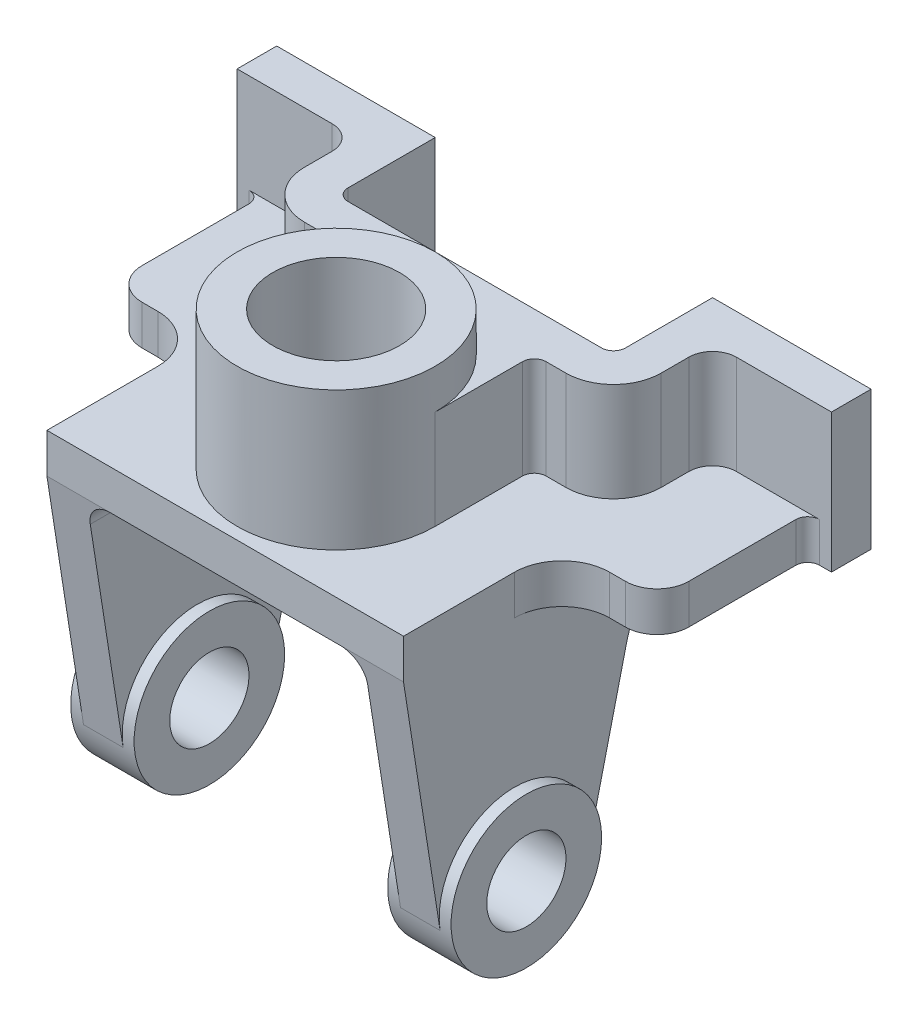
SolidWorks part; units mm, degrees
ref_plane "Front Plane" through (0, 0, 0) normal (0, 0, 1) x (1, 0, 0)
ref_plane "Top Plane" through (0, 0, 0) normal (0, 1, 0) x (1, 0, 0)
ref_plane "Right Plane" through (0, 0, 0) normal (1, 0, 0) x (0, 0, -1)
sketch "Sketch2" plane through (0, 0, 0) normal (0, 1, 0) x (1, 0, 0)
  line L0 (-25, 0) -> (-25, 22)
  line L1 (-28, 25) -> (-33, 25)
  line L2 (-45, 37) -> (-45, 44)
  line L3 (-72, 50) -> (-75, 50)
  line L4 (-75, 50) -> (-75, 60)
  line L5 (-75, 60) -> (-35, 60)
  line L6 (-35, 60) -> (-35, 38)
  line L7 (25, 0) -> (25, 22)
  line L8 (28, 25) -> (33, 25)
  line L9 (45, 37) -> (45, 44)
  line L10 (72, 50) -> (75, 50)
  line L11 (75, 50) -> (75, 60)
  line L12 (75, 60) -> (35, 60)
  line L13 (35, 60) -> (35, 38)
  line L14 (32, 35) -> (-32, 35)
  line L15 (0, 0) -> (0, 35) construction
  line L16 (-69, 47) -> (-69, 20)
  line L17 (0, 0) -> (0, 25) construction
  line L18 (-75, 60) -> (75, 60) construction
  line L19 (-61, 12) -> (-57, 12)
  line L20 (-45, 0) -> (-45, -28)
  line L21 (-45, -28) -> (45, -28)
  line L22 (45, -28) -> (45, 0)
  line L23 (57, 12) -> (61, 12)
  line L24 (69, 20) -> (69, 47)
  line L25 (0, 0) -> (0, -28) construction
  line L26 (-69, 12) -> (69, 12) construction
  line L27 (0, 0) -> (0, 8) construction
  line L28 (0, 0) -> (0, 8) construction
  line L29 (51, 50) -> (72, 50)
  line L30 (-51, 50) -> (-72, 50)
  circle A0 centre (0, 0) radius 25
  arc A1 (-33, 25) -> (-45, 37) centre (-33, 37) cw
  arc A2 (45, 37) -> (33, 25) centre (33, 37) cw
  arc A3 (25, 22) -> (28, 25) centre (28, 22) cw
  arc A4 (-25, 22) -> (-28, 25) centre (-28, 22) ccw
  arc A5 (45, 44) -> (51, 50) centre (51, 44) cw
  arc A6 (-45, 44) -> (-51, 50) centre (-51, 44) ccw
  arc A7 (35, 38) -> (32, 35) centre (32, 38) cw
  arc A8 (-32, 35) -> (-35, 38) centre (-32, 38) cw
  arc A9 (-45, 0) -> (-57, 12) centre (-57, 0) ccw
  arc A10 (45, 0) -> (57, 12) centre (57, 0) cw
  arc A11 (-61, 12) -> (-69, 20) centre (-61, 20) cw
  arc A12 (61, 12) -> (69, 20) centre (61, 20) ccw
  arc A13 (69, 47) -> (72, 50) centre (72, 47) cw
  arc A14 (-69, 47) -> (-72, 50) centre (-72, 47) ccw
  point P23 (-45, 25)
  point P26 (45, 25)
  point P29 (25, 25)
  point P38 (35, 35)
  point P41 (-35, 35)
  dimension "D1" = 50
  dimension "D15" = 12
  dimension "D16" = 3
  dimension "D17" = 6
  dimension "D18" = 3
  dimension "D24" = 12
  dimension "D25" = 8
  dimension "D27" = 3
  dimension "D28" = 3
  dimension "D2" = 70
  dimension "D3" = 90
  dimension "D4" = 10
  dimension "D5" = 75
  dimension "D6" = 75
  dimension "D7" = 60
  dimension "D8" = 60
  dimension "D9" = 25
  dimension "D10" = 10
  dimension "D11" = 10
  dimension "D12" = 25
  dimension "D13" = 20
  dimension "D14" = 10
  dimension "D19" = 90
  dimension "D20" = 69
  dimension "D21" = 69
  dimension "D22" = 38
  dimension "D23" = 40
  dimension "D26" = 27
extrude "Boss-Extrude2" add sketch "Sketch2" along normal blind 35 contours L14 A8 L6 L5 L4 L3 L30 A6 L2 A1 L1 A4 L0 A0 L7 A3 L8 A2 L9 A5 L29 L10 L11 L12 L13 A7 region at (-23.3845, 0, -11)
extrude "Boss-Extrude3" add sketch "Sketch2<3>" along normal blind 10 contours A14 L16 A11 L19 A9 L20 L21 L22 A10 L23 A12 L24 A13 L29 A5 L9 A2 L8 A3 L7 A0 L0 A4 L1 A1 L2 A6 L30 region at (0, 0, 26.6377)
sketch "Sketch2<3>" plane through (0, 0, 0) normal (0, 1, 0) x (1, 0, 0) same geometry as "Sketch2"
sketch "Sketch3" plane through (0, 0, 0) normal (0, -1, 0) x (1, 0, 0)
  circle A0 centre (0, 0) radius 16
  circle A1 centre (0, 0) radius 25 construction
  circle A2 centre (0, 0) radius 25
  dimension "D1" = 32
extrude "Boss-Extrude4" add sketch "Sketch3" against normal blind 45
sketch "Sketch4" plane through (45, 0, 0) normal (1, 0, 0) x (0, 0, -1)
  line L0 (0, -56) -> (0, 0) construction
  line L1 (-28, 0) -> (-18.7713, -58.9392)
  line L2 (-28, 10) -> (0, 10) construction
  line L3 (20, 0) -> (47, 0) construction
  line L4 (28.3956, -19.1579) -> (18.4739, -60.44)
  line L5 (-28, 0) -> (33, 0)
  line L6 (52.7034, 0) -> (60, 0)
  line L7 (33, 0) -> (52.7034, 0)
  circle A0 centre (0, -56) radius 10
  circle A1 centre (0, -56) radius 19
  arc A2 (28.3956, -19.1579) -> (52.7034, 0) centre (52.7034, -25) cw
  point P6 (33, 0)
  line M6 (-28, 0) -> (0, 0)
  dimension "D1" = 20
  dimension "D2" = 38
  dimension "D6" = 25
  dimension "D3" = 56
  dimension "D4" = 10
  dimension "D5" = 33
extrude "Boss-Extrude5" add sketch "Sketch4" against normal blind 10 contours A1 L0 L1 M6 | L0 A1 L4 A2 L7 L5 region at (45, -20.3618, 13.0036) region at (45, -19.3397, -15.9916)
extrude "Boss-Extrude6" add sketch "Sketch4<3>" along normal blind 3 and the other way blind 13 contours A0 A1 region at (45, -37.593, 1.4324)
sketch "Sketch4<3>" plane through (45, 0, 0) normal (1, 0, 0) x (0, 0, -1) same geometry as "Sketch4"
mirror "Mirror1" about plane through (0, 0, 0) normal (1, 0, 0) of "Boss-Extrude5", "Boss-Extrude6"
fillet "Fillet1" radius 6 2 edges at (35, 0, -5) (-35, 0, -5)
